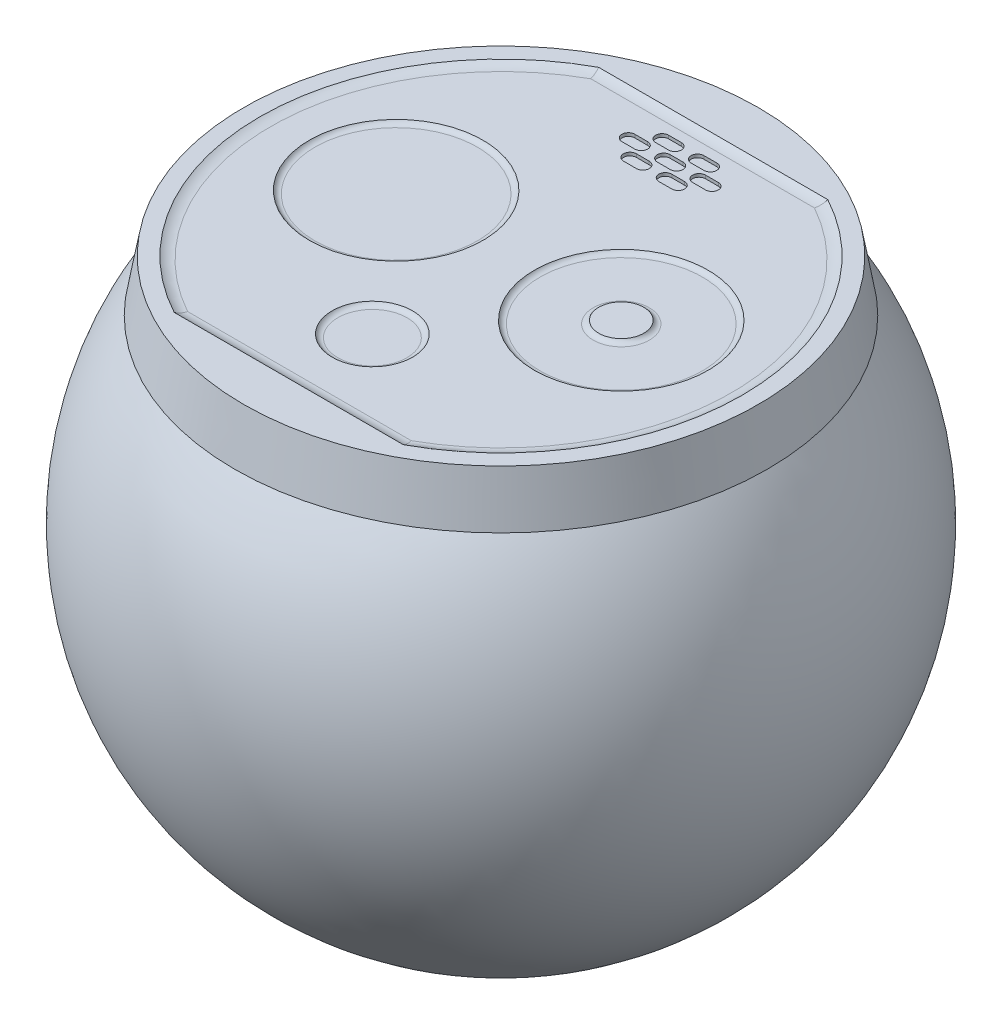
SolidWorks part; units mm, degrees
material "ABS"
ref_plane "Alzado" through (0, 0, 0) normal (0, 0, 1) x (1, 0, 0)
ref_plane "Planta" through (0, 0, 0) normal (0, 1, 0) x (1, 0, 0)
ref_plane "Vista lateral" through (0, 0, 0) normal (1, 0, 0) x (0, 0, -1)
sketch "Sketch1" plane through (0, 0, 0) normal (1, 0, 0) x (0, 0, -1)
  line L3 (40, 36) -> (41.4246, 28)
  line L4 (0, 36) -> (0, -50) construction
  line L5 (0, 36) -> (40, 36)
  line L6 (0, 36) -> (0, -50)
  arc A0 (0, -50) -> (41.4246, 28) centre (0, 0) ccw
  dimension "D1" = 100
  dimension "D2" = 28
  dimension "D3" = 80
  dimension "D4" = 36
revolve "Revolve1" add sketch "Sketch1" angle 360 about L4
sketch "Sketch2" plane through (0, 36, 0) normal (0, 1, 0) x (1, 0, 0)
  line L0 (89.3493, -112.6457) -> (674.016, -112.6457) construction
  line L1 (-17.8115, 33) -> (17.8115, 33)
  line L2 (-17.8115, -33) -> (17.8115, -33)
  circle A0 centre (0, 0) radius 37.5
  dimension "D1" = 75
  dimension "D2" = 33
extrude "Extrude1" cut sketch "Sketch2" against normal blind 0.5 contours L2 A0 L1 region at (0, 36, 0)
fillet "Fillet1" radius 3 4 edges at (0, 35.5, 33) (37.5, 35.5, 0) (0, 35.5, -33) (-37.5, 35.5, 0)
sketch "Sketch3" plane through (0, 35.5, 0) normal (0, 1, 0) x (1, 0, 0)
  line L0 (-3.75, 23.8) -> (-1.75, 23.8) construction
  line L1 (-3.75, 24.8) -> (-1.75, 24.8)
  line L2 (-3.75, 22.8) -> (-1.75, 22.8)
  line L3 (-6.5, 26.3) -> (-4.5, 26.3) construction
  line L4 (-1, 26.3) -> (1, 26.3) construction
  line L5 (-6.5, 27.3) -> (-4.5, 27.3)
  line L6 (-6.5, 25.3) -> (-4.5, 25.3)
  line L7 (-1, 27.3) -> (1, 27.3)
  line L8 (-1, 25.3) -> (1, 25.3)
  line L9 (-3.75, 28.8) -> (-1.75, 28.8) construction
  line L10 (-3.75, 29.8) -> (-1.75, 29.8)
  line L11 (-3.75, 27.8) -> (-1.75, 27.8)
  line L12 (1.75, 28.8) -> (3.75, 28.8) construction
  line L13 (1.75, 29.8) -> (3.75, 29.8)
  line L14 (1.75, 27.8) -> (3.75, 27.8)
  line L15 (4.5, 26.3) -> (6.5, 26.3) construction
  line L16 (4.5, 27.3) -> (6.5, 27.3)
  line L17 (4.5, 25.3) -> (6.5, 25.3)
  line L18 (1.75, 23.8) -> (3.75, 23.8) construction
  line L19 (1.75, 24.8) -> (3.75, 24.8)
  line L20 (1.75, 22.8) -> (3.75, 22.8)
  line L21 (-2.75, 23.8) -> (2.75, 23.8) construction
  line L22 (-17.5, 1.2) -> (17.5, 1.2) construction
  circle A0 centre (-17.5, 1.2) radius 13.5
  circle A1 centre (17.5, 1.2) radius 13.5
  circle A2 centre (17.5, 1.2) radius 3.5
  circle A3 centre (0, -20) radius 6.25
  arc A4 (-3.75, 24.8) -> (-3.75, 22.8) centre (-3.75, 23.8) ccw
  arc A5 (-1.75, 22.8) -> (-1.75, 24.8) centre (-1.75, 23.8) ccw
  arc A6 (-6.5, 27.3) -> (-6.5, 25.3) centre (-6.5, 26.3) ccw
  arc A7 (-4.5, 25.3) -> (-4.5, 27.3) centre (-4.5, 26.3) ccw
  arc A8 (-1, 27.3) -> (-1, 25.3) centre (-1, 26.3) ccw
  arc A9 (1, 25.3) -> (1, 27.3) centre (1, 26.3) ccw
  arc A10 (-3.75, 29.8) -> (-3.75, 27.8) centre (-3.75, 28.8) ccw
  arc A11 (-1.75, 27.8) -> (-1.75, 29.8) centre (-1.75, 28.8) ccw
  arc A12 (1.75, 29.8) -> (1.75, 27.8) centre (1.75, 28.8) ccw
  arc A13 (3.75, 27.8) -> (3.75, 29.8) centre (3.75, 28.8) ccw
  arc A14 (4.5, 27.3) -> (4.5, 25.3) centre (4.5, 26.3) ccw
  arc A15 (6.5, 25.3) -> (6.5, 27.3) centre (6.5, 26.3) ccw
  arc A16 (1.75, 24.8) -> (1.75, 22.8) centre (1.75, 23.8) ccw
  arc A17 (3.75, 22.8) -> (3.75, 24.8) centre (3.75, 23.8) ccw
  point P9 (-2.75, 23.8)
  point P18 (-5.5, 26.3)
  point P23 (0, 26.3)
  point P28 (-2.75, 28.8)
  point P35 (2.75, 28.8)
  point P42 (5.5, 26.3)
  point P49 (2.75, 23.8)
  point P56 (0, 23.8)
  point P57 (0, 1.2)
  dimension "D1" = 2
  dimension "D2" = 1
  dimension "D9" = 27
  dimension "D10" = 7
  dimension "D13" = 20
  dimension "D14" = 12.5
  dimension "D3" = 5.5
  dimension "D4" = 2.5
  dimension "D5" = 2.5
  dimension "D6" = 5.5
  dimension "D7" = 5.5
  dimension "D8" = 26.3
  dimension "D11" = 1.2
  dimension "D12" = 35
extrude "Extrude2" cut sketch "Sketch3" against normal blind 0.5
fillet "Fillet2" radius 1 4 edges at (0, 35, 26.25) (17.5, 35, 12.3) (17.5, 35, 2.3) (-17.5, 35, 12.3)
